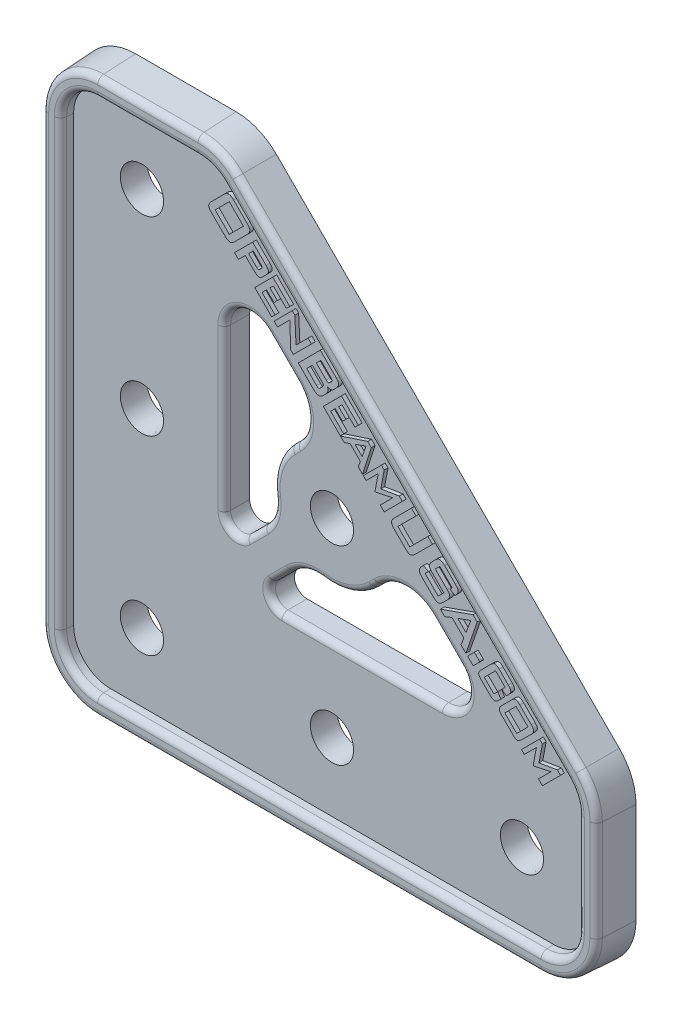
SolidWorks part; units mm, degrees
ref_plane "Front Plane" through (0, 0, 0) normal (0, 0, 1) x (1, 0, 0)
ref_plane "Top Plane" through (0, 0, 0) normal (0, 1, 0) x (1, 0, 0)
ref_plane "Right Plane" through (0, 0, 0) normal (1, 0, 0) x (0, 0, -1)
sketch "Sketch1" plane through (0, 0, 0) normal (0, 0, 1) x (1, 0, 0)
  line L0 (16.4645, 43.5355) -> (43.5355, 16.4645)
  line L1 (5, 0) -> (40, 0)
  line L2 (0, 5) -> (0, 40)
  line L3 (5, 45) -> (12.9289, 45)
  line L4 (45, 5) -> (45, 12.9289)
  arc A0 (0, 5) -> (5, 0) centre (5, 5) ccw
  arc A1 (45, 5) -> (40, 0) centre (40, 5) cw
  arc A2 (45, 12.9289) -> (43.5355, 16.4645) centre (40, 12.9289) ccw
  arc A3 (16.4645, 43.5355) -> (12.9289, 45) centre (12.9289, 40) ccw
  arc A4 (5, 45) -> (0, 40) centre (5, 40) ccw
  point P8 (0, 0)
  point P11 (45, 0)
  point P14 (45, 15)
  point P19 (0, 45)
  dimension "D4" = 5
  dimension "D1" = 45
  dimension "D2" = 45
  dimension "D3" = 15
extrude "Boss-Extrude1" add sketch "Sketch1" along normal blind 2 draft 3
sketch "Sketch2" plane through (0, 0, 2) normal (0, 0, 1) x (1, 0, 0)
  line L0 (7.5, 7.5) -> (58.6399, 7.5) construction
  line L2 (55, 0) -> (-55, 0) construction
  line L4 (7.5, 40) -> (7.5, 5)
  line L5 (7.5, 40) -> (7.5, 7.5) construction
  circle A0 centre (7.5, 37.5) radius 1.6
  circle A1 centre (7.5, 7.5) radius 1.6
  circle A2 centre (7.5, 22.5) radius 1.6
  circle A3 centre (22.5, 7.5) radius 1.6
  circle A4 centre (37.5, 7.5) radius 1.6
  dimension "D7" = 3.2
  dimension "D1" = 7.5
  dimension "D2" = 7.5
  dimension "D3" = 15
  dimension "D4" = 15
  dimension "D5" = 15
  dimension "D6" = 15
extrude "Cut-Extrude1" cut sketch "Sketch2" against normal blind 2
other "Move Face1" flip direction yes face at (2.0139, 2.0139, 1) face at (22.5, 0.0524, 1) face at (42.9861, 2.0139, 1) face at (44.9476, 8.9645, 1) face at (44.397, 14.7502, 1) face at (29.9629, 29.9629, 1) face at (14.7502, 44.397, 1) face at (8.9645, 44.9476, 1) face at (2.0139, 42.9861, 1) face at (0.0524, 22.5, 1) offset 0.5 parameters "D1"=0.5
sketch "Sketch3" plane through (0, 0, 2) normal (0, 0, 1) x (1, 0, 0)
  line L5 (5, 2.1055) -> (40, 2.1055)
  line L6 (42.8945, 5) -> (42.8945, 12.9289)
  line L7 (42.0467, 14.9757) -> (14.9757, 42.0467)
  line L8 (12.9289, 42.8945) -> (5, 42.8945)
  line L9 (2.1055, 40) -> (2.1055, 5)
  line L10 (5, 0.6055) -> (40, 0.6055)
  line L11 (44.3945, 5) -> (44.3945, 12.9289)
  line L12 (43.1074, 16.0363) -> (16.0363, 43.1074)
  line L13 (12.9289, 44.3945) -> (5, 44.3945)
  line L14 (0.6055, 40) -> (0.6055, 5)
  line L15 (5, 0.6055) -> (40, 0.6055)
  line L16 (44.3945, 5) -> (44.3945, 12.9289)
  line L17 (43.1074, 16.0363) -> (16.0363, 43.1074)
  line L18 (12.9289, 44.3945) -> (5, 44.3945)
  line L19 (0.6055, 40) -> (0.6055, 5)
  arc A5 (40, 2.1055) -> (42.8945, 5) centre (40, 5) ccw
  arc A6 (42.8945, 12.9289) -> (42.0467, 14.9757) centre (40, 12.9289) ccw
  arc A7 (14.9757, 42.0467) -> (12.9289, 42.8945) centre (12.9289, 40) ccw
  arc A8 (5, 42.8945) -> (2.1055, 40) centre (5, 40) ccw
  arc A9 (2.1055, 5) -> (5, 2.1055) centre (5, 5) ccw
  arc A10 (0.6055, 5) -> (5, 0.6055) centre (5, 5) ccw
  arc A11 (40, 0.6055) -> (44.3945, 5) centre (40, 5) ccw
  arc A12 (44.3945, 12.9289) -> (43.1074, 16.0363) centre (40, 12.9289) ccw
  arc A13 (16.0363, 43.1074) -> (12.9289, 44.3945) centre (12.9289, 40) ccw
  arc A14 (5, 44.3945) -> (0.6055, 40) centre (5, 40) ccw
  arc A15 (0.6055, 5) -> (5, 0.6055) centre (5, 5) ccw
  arc A16 (40, 0.6055) -> (44.3945, 5) centre (40, 5) ccw
  arc A17 (44.3945, 12.9289) -> (43.1074, 16.0363) centre (40, 12.9289) ccw
  arc A18 (16.0363, 43.1074) -> (12.9289, 44.3945) centre (12.9289, 40) ccw
  arc A19 (5, 44.3945) -> (0.6055, 40) centre (5, 40) ccw
  dimension "D2" = 1.5
  dimension "D1" = 0
extrude "Boss-Extrude2" add sketch "Sketch3" along normal blind 1 draft 3
fillet "Fillet1" radius 0.5 20 edges at (42.0838, 2.9162, 3) (42.9469, 8.9645, 3) (42.7226, 14.0567, 3) (28.5482, 28.5482, 3) (14.0567, 42.7226, 3) (8.9645, 42.9469, 3) (2.9162, 42.0838, 3) (2.0531, 22.5, 3) (2.9162, 2.9162, 3) (22.5, 2.0531, 3) (0.6579, 22.5, 3) (1.9297, 43.0703, 3) (8.9645, 44.3421, 3) (14.5906, 44.0116, 3) (29.5348, 29.5348, 3) (44.0116, 14.5906, 3) (44.3421, 8.9645, 3) (43.0703, 1.9297, 3) (22.5, 0.6579, 3) (1.9297, 1.9297, 3)
sketch "Sketch7" plane through (0, 0, 2) normal (0, 0, 1) x (1, 0, 0)
  line L0 (7.5, 37.5) -> (37.5, 7.5) construction
  circle A0 centre (22.5, 22.5) radius 1.6
  circle A1 centre (7.5, 37.5) radius 1.6 construction
extrude "Cut-Extrude4" cut sketch "Sketch7" against normal through all
sketch "Sketch5" plane through (0, 0, 2) normal (0, 0, 1) x (1, 0, 0)
  line L0 (14, 31.2042) -> (14, 18.5355)
  line L1 (18.5355, 14) -> (31.2042, 14)
  line L2 (32.638, 17.4615) -> (30.4238, 19.6758)
  line L3 (42.0467, 14.9757) -> (14.9757, 42.0467) construction
  line L4 (0, -54.6431) -> (0, 54.6431) construction
  line L5 (55, 0) -> (-55, 0) construction
  line L6 (43.1815, 16.1104) -> (16.1104, 43.1815) construction
  line L7 (19.2473, 25.7527) -> (19.6758, 26.1811)
  line L8 (25.7527, 19.2473) -> (26.1811, 19.6758)
  line L9 (19.6758, 30.4238) -> (17.4615, 32.638)
  line L10 (22.5, 22.5) -> (7.5, 7.5) construction
  line L11 (15.7071, 17.8284) -> (17.1086, 19.23)
  line L12 (17.8284, 15.7071) -> (19.23, 17.1086)
  arc A0 (21.8047, 17.9528) -> (25.7527, 19.2473) centre (22.5, 22.5) ccw
  arc A1 (31.2042, 14) -> (32.638, 17.4615) centre (31.2042, 16.0277) ccw
  arc A2 (17.4615, 32.638) -> (14, 31.2042) centre (16.0277, 31.2042) ccw
  arc A4 (26.1811, 19.6758) -> (30.4238, 19.6758) centre (28.3025, 17.5544) cw
  circle A5 centre (22.5, 22.5) radius 4.6
  arc A6 (19.2473, 25.7527) -> (17.9528, 21.8047) centre (22.5, 22.5) ccw
  arc A7 (19.6758, 26.1811) -> (19.6758, 30.4238) centre (17.5544, 28.3025) ccw
  arc A8 (21.8047, 17.9528) -> (19.23, 17.1086) centre (21.3513, 14.9873) ccw
  arc A9 (17.9528, 21.8047) -> (17.1086, 19.23) centre (14.9873, 21.3513) cw
  arc A10 (14, 18.5355) -> (15.7071, 17.8284) centre (15, 18.5355) ccw
  arc A11 (18.5355, 14) -> (17.8284, 15.7071) centre (18.5355, 15) cw
  point P27 (21.7971, 28.3025)
  point P32 (20.4858, 18.3644)
  dimension "D4" = 3
  dimension "D6" = 3
  dimension "D8" = 1
  dimension "D9" = 1
  dimension "D1" = 14
  dimension "D2" = 14
  dimension "D3" = 6.5
  dimension "D7" = 3
  dimension "D5" = 3
extrude "Cut-Extrude2" cut sketch "Sketch5" against normal through all
fillet "Fillet3" radius 0.5 18 edges at (17.6117, 14.6173, 2) (18.5292, 16.4079, 2) (20.4166, 17.838, 2) (23.9332, 18.129, 2) (25.9669, 19.4615, 2) (28.3025, 20.5544, 2) (31.5309, 18.5687, 2) (33.0775, 15.2518, 2) (16.4079, 18.5292, 2) (14.6173, 17.6117, 2) (14, 24.8698, 2) (15.2518, 33.0775, 2) (18.5687, 31.5309, 2) (20.5544, 28.3025, 2) (19.4615, 25.9669, 2) (18.129, 23.9332, 2) (24.8698, 14, 2) (17.838, 20.4166, 2)
sketch "Sketch8" plane through (0, 0, 2) normal (0, 0, 1) x (1, 0, 0)
  line L0 (12.2209, 40) -> (40, 12.2209) construction
  line L1 (17.8151, 32.9915) -> (20.0293, 30.7773) construction
  line L5 (40, 2.0779) -> (40, 1.5786) construction
  text T0 "OpenBeamUSA.com" font "BankGothic Md BT" height 2.5
  dimension "D1" = 1
extrude "Boss-Extrude3" add sketch "Sketch8" along normal blind 0.3
sketch "Sketch6" plane through (0, 0, 0) normal (0, 0, -1) x (-1, 0, 0)
  line L0 (-44.7584, 10.9979) -> (-10.2693, 45.4871) construction
  line L1 (-43.1815, 16.1104) -> (-16.1104, 43.1815) construction
  line L2 (-39.1919, 18.6858) -> (-18.6858, 39.1919)
  line L3 (-17.9787, 39.1919) -> (-16.5645, 37.7777)
  line L4 (-16.5645, 37.0706) -> (-37.0706, 16.5645)
  line L5 (-37.7777, 16.5645) -> (-39.1919, 17.9787)
  line L6 (-22.5, 22.5) -> (-29.5523, 29.5523) construction
  line L8 (-16.0168, 43.0879) -> (-43.0879, 16.0168) construction
  arc A0 (-39.1919, 18.6858) -> (-39.1919, 17.9787) centre (-38.8383, 18.3323) ccw
  arc A1 (-37.0706, 16.5645) -> (-37.7777, 16.5645) centre (-37.4241, 16.918) cw
  arc A2 (-16.5645, 37.7777) -> (-16.5645, 37.0706) centre (-16.918, 37.4241) cw
  arc A3 (-18.6858, 39.1919) -> (-17.9787, 39.1919) centre (-18.3323, 38.8383) cw
  point P12 (-37.4241, 16.2109)
  point P15 (-16.2109, 37.4241)
  point P18 (-18.3323, 39.5455)
  dimension "D3" = 0.5
  dimension "D1" = 30
  dimension "D2" = 3
  dimension "D4" = 1
extrude "Cut-Extrude3" cut sketch "Sketch6" against normal blind 0.2 draft 3
sketch "Sketch10" plane through (0, 0, 0.2) normal (0, 0, -1) x (-1, 0, 0)
  line L0 (-37.7777, 16.5645) -> (-16.5645, 37.7777) construction
  text T0 "TL625-000100-001" font "Arial" height 2
split line "Split Line1"
draft "Draft1" type of draft neutral plane draft angle 3 faces to draft 6 face at (24.1, 22.5, 0) face at (39.1, 7.5, 0) face at (24.1, 7.5, 0) face at (9.1, 7.5, 0) face at (9.1, 22.5, 0) face at (9.1, 37.5, 0) neutral plane through (5, 5, 0) neutral plane normal (0, 0, -1) reverse direction yes parameters "D1"=3
sketch "Alignment_Sketch" plane through (0, 0, 0) normal (0, 0, -1) x (-1, 0, 0)
  line L0 (-7.5, 37.5) -> (-7.5, 7.5) construction
  line L1 (-7.5, 7.5) -> (-37.5, 7.5) construction
  line L2 (-37.5, 7.5) -> (-7.5, 37.5) construction
  point P0 (-7.5, 37.5)
  point P1 (-7.5, 7.5)
  point P3 (-22.5, 7.5)
  point P5 (-37.5, 7.5)
  point P7 (-22.5, 22.5)
  point P9 (-7.5, 22.5)
